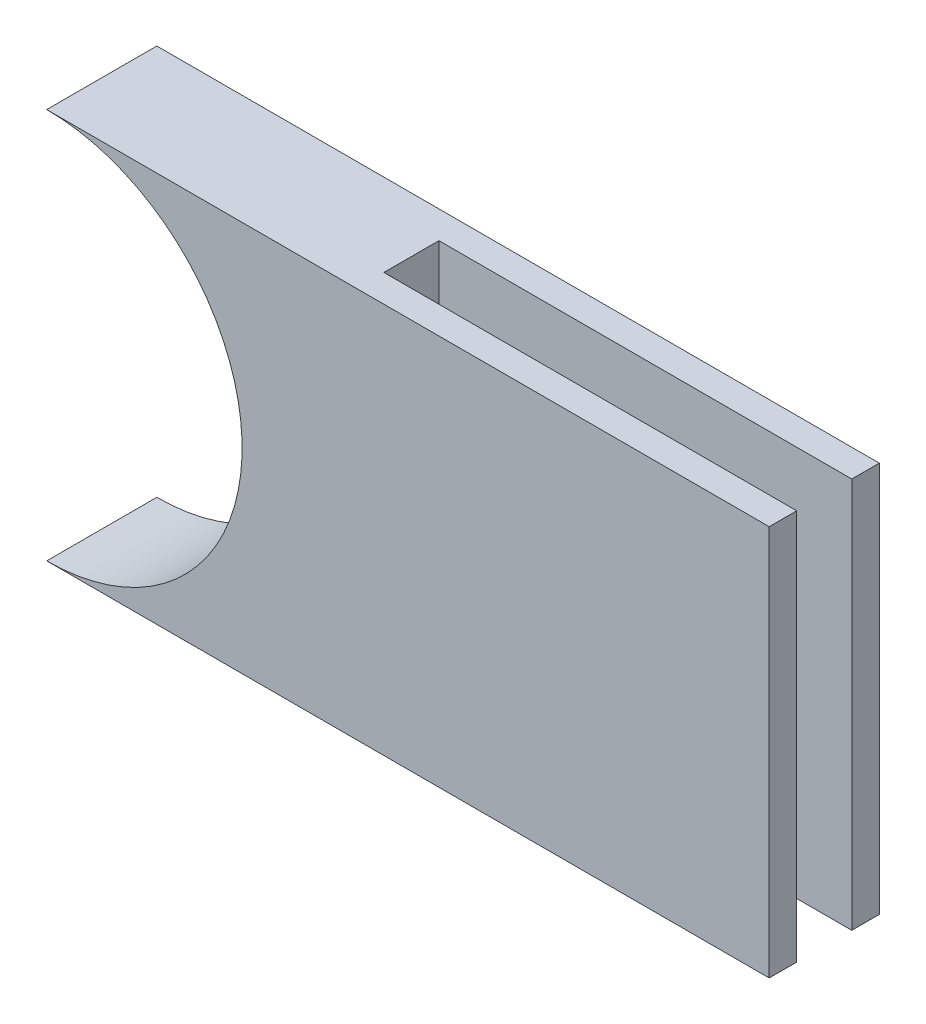
SolidWorks part; units mm, degrees
ref_plane "Front Plane" through (0, 0, 0) normal (0, 0, 1) x (1, 0, 0)
ref_plane "Top Plane" through (0, 0, 0) normal (0, 1, 0) x (1, 0, 0)
ref_plane "Right Plane" through (0, 0, 0) normal (1, 0, 0) x (0, 0, -1)
sketch "Sketch1" plane through (0, 0, 0) normal (0, 0, 1) x (1, 0, 0)
  circle A0 centre (0, 0) radius 19.939
  dimension "D1" = 39.878
extrude "circle extrude" add sketch "Sketch1" along normal blind 7.62
sketch "Sketch3" plane through (0, 0, 0) normal (1, 0, 0) x (0, 0, -1)
  line L0 (0, 19.8374) -> (0, -19.8374) construction
  line L1 (-7.62, 19.939) -> (0, 19.939)
  line L2 (-7.62, 19.939) -> (-7.62, -19.939)
  line L3 (-7.62, -19.939) -> (0, -19.939)
  line L4 (0, 19.939) -> (0, -19.939)
  line L5 (-7.62, -19.939) -> (0, -19.939) construction
extrude "rectangle extrude" add sketch "Sketch3" along normal blind 68.58
sketch "Sketch2" plane through (0, 0, 7.62) normal (0, 0, 1) x (1, 0, 0)
  circle A0 centre (0, 0) radius 18.034
  dimension "D1" = 36.068
extrude "cricle cut" cut sketch "Sketch2" against normal through all
sketch "Sketch4" plane through (0, 0, 7.62) normal (0, 0, 1) x (1, 0, 0)
  line L0 (68.58, 19.939) -> (68.58, -19.939) construction
  line L1 (0, 18.034) -> (66.675, 18.034)
  line L2 (0, 18.034) -> (0, -18.034)
  line L3 (0, -18.034) -> (66.675, -18.034)
  line L4 (66.675, 18.034) -> (66.675, -18.034)
  line L5 (68.58, -19.939) -> (0, -19.939) construction
  circle A0 centre (0, 0) radius 18.034 construction
  dimension "D1" = 1.905
  dimension "D2" = 1.905
extrude "frame cut" cut sketch "Sketch4" against normal through all flip side to cut
sketch "Sketch8" plane through (0, 0, 7.62) normal (0, 0, 1) x (1, 0, 0)
  line L6 (0, -18.034) -> (66.675, -18.034) construction
  line L7 (36.068, 18.034) -> (66.675, 18.034)
  line L8 (66.675, 18.034) -> (66.675, -18.034)
  line L9 (66.675, -18.034) -> (36.068, -18.034)
  line L10 (66.675, 18.034) -> (0, 18.034) construction
  arc A1 (36.068, -18.034) -> (36.068, 18.034) centre (36.068, 0) ccw
  dimension "D1" = 36.068
extrude "end cut" [suppressed] cut sketch "Sketch8" against normal through all
sketch "Sketch10" plane through (0, 0, 0) normal (0, 0, -1) x (-1, 0, 0)
  line L2 (0, 18.034) -> (-66.675, 18.034)
  line L3 (-66.675, -18.034) -> (0, -18.034)
  line L4 (0, 18.034) -> (-66.675, 18.034)
  line L5 (-66.675, -18.034) -> (0, -18.034)
  line L7 (-66.675, 18.034) -> (-66.675, -18.034)
  line L8 (-66.675, 18.034) -> (-66.675, -18.034)
  arc A3 (0, 18.034) -> (0, -18.034) centre (0, 0) ccw
  arc A5 (0, 18.034) -> (0, -18.034) centre (0, 0) ccw
  dimension "D1" = 0
extrude "extension" add sketch "Sketch10" along normal blind 2.54
ref_plane "Plane2" [suppressed] through (20.32, 0, 0) normal (1, 0, 0) x (0, 0, -1)
sketch "Sketch11" [suppressed] plane through (20.32, 0, 0) normal (1, 0, 0) x (0, 0, -1)
  line L0 (2.54, 18.034) -> (-7.62, 18.034) construction
  line L1 (0, -18.034) -> (-5.08, -18.034)
  line L2 (0, -18.034) -> (0, 18.034)
  line L3 (0, 18.034) -> (-5.08, 18.034)
  line L4 (-5.08, -18.034) -> (-5.08, 18.034)
  line L5 (0, -18.034) -> (-5.08, 18.034) construction
  line L6 (0, 18.034) -> (-5.08, -18.034) construction
  line L7 (2.54, -18.034) -> (-7.62, -18.034) construction
  point P0 (-2.54, 0)
  dimension "D1" = 2.54
  dimension "D2" = 5.08
extrude "middle" [suppressed] cut sketch "Sketch11" along normal through all
sketch "Sketch12" [suppressed] plane through (0, 0, 0) normal (0, 0, 1) x (1, 0, 0)
  line L0 (20.32, -5.588) -> (20.32, 5.588) construction
  line L1 (0, 18.034) -> (61.595, 18.034) construction
  line L2 (2.286, 18.034) -> (0, 18.034)
  line L3 (0, 18.034) -> (0, -18.034)
  line L4 (0, -18.034) -> (2.286, -18.034)
  arc A0 (2.286, -18.034) -> (2.286, 18.034) centre (2.286, 0) ccw
  dimension "D1" = 36.068
extrude "circle extension" [suppressed] cut sketch "Sketch12" along normal blind 5.08 flip side to cut
sketch "Sketch13" plane through (66.675, 0, 0) normal (1, 0, 0) x (0, 0, -1)
  line L1 (0, -18.034) -> (-5.08, -18.034)
  line L2 (0, -18.034) -> (0, 18.034)
  line L3 (0, 18.034) -> (-5.08, 18.034)
  line L4 (-5.08, -18.034) -> (-5.08, 18.034)
  line L5 (0, -18.034) -> (-5.08, 18.034) construction
  line L6 (0, 18.034) -> (-5.08, -18.034) construction
  line L7 (2.54, -18.034) -> (-7.62, -18.034) construction
  line L8 (2.54, 18.034) -> (-7.62, 18.034) construction
  point P0 (-2.54, 0)
  dimension "D1" = 2.54
  dimension "D2" = 5.08
extrude "Cut-Extrude1" cut sketch "Sketch13" against normal blind 38.1
sketch "Sketch14" plane through (28.575, 0, 0) normal (1, 0, 0) x (0, 0, -1)
  circle A0 centre (-2.54, 0) radius 1.905
  dimension "D2" = 3.81
  dimension "D1" = 2.54
extrude "Boss-Extrude3" add sketch "Sketch14" along normal blind 2.54
